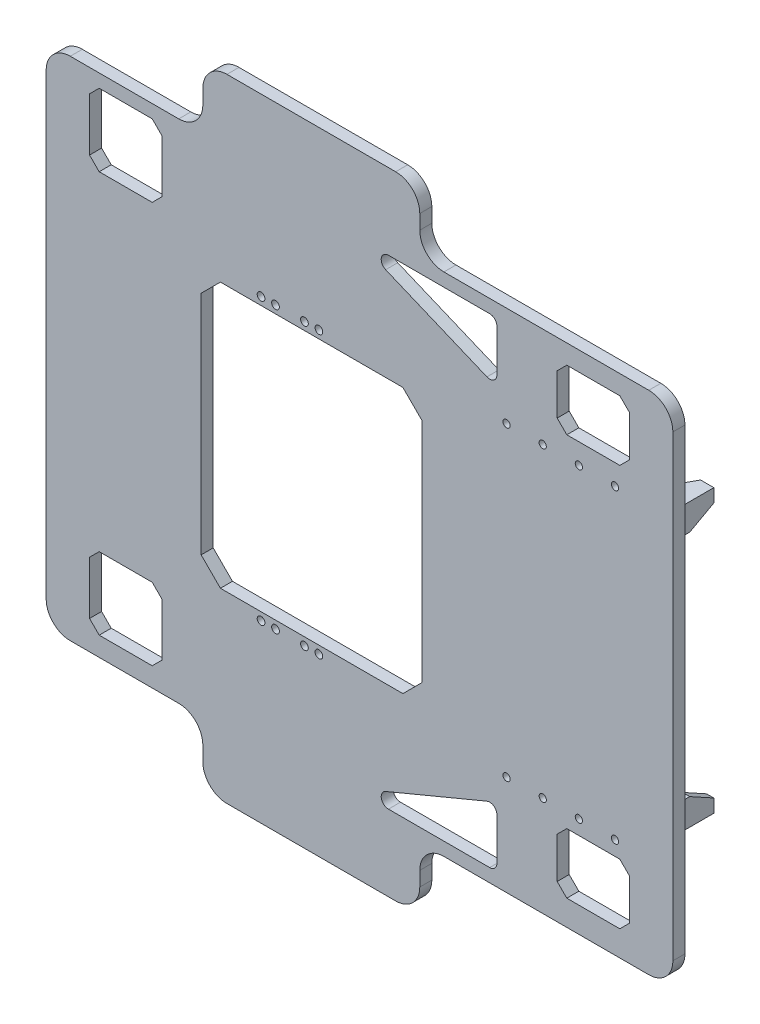
SolidWorks part; units mm, degrees
ref_plane "前视基准面" through (0, 0, 0) normal (0, 0, 1) x (1, 0, 0)
ref_plane "上视基准面" through (0, 0, 0) normal (0, 1, 0) x (1, 0, 0)
ref_plane "右视基准面" through (0, 0, 0) normal (1, 0, 0) x (0, 0, -1)
sketch "草图1" plane through (0, 0, 0) normal (0, 0, 1) x (1, 0, 0)
  line L2 (-130, 95) -> (-130, -95)
  line L3 (-120, -105) -> (-75, -105)
  line L4 (130, 95) -> (130, -95)
  line L5 (126.7518, 102.3765) -> (130, 105) construction
  line L6 (-130, -105) -> (-126.7518, -102.3765) construction
  line L9 (-65, -115) -> (-65, -121)
  line L10 (-55, -131) -> (15, -131)
  line L11 (25, -121) -> (25, -115)
  line L13 (35, -105) -> (120, -105)
  line L14 (126.7518, -102.3765) -> (130, -105) construction
  line L15 (-130, 105) -> (-126.7518, 102.3765) construction
  line L16 (-130, 0) -> (130, 0) construction
  line L17 (35, 105) -> (120, 105)
  line L18 (25, 121) -> (25, 115)
  line L19 (-55, 131) -> (15, 131)
  line L20 (-65, 115) -> (-65, 121)
  line L21 (-120, 105) -> (-75, 105)
  arc A1 (-120, -105) -> (-130, -95) centre (-120, -95) cw
  arc A3 (120, -105) -> (130, -95) centre (120, -95) ccw
  arc A8 (-65, -115) -> (-75, -105) centre (-75, -115) ccw
  arc A9 (25, -115) -> (35, -105) centre (35, -115) cw
  arc A10 (-55, -131) -> (-65, -121) centre (-55, -121) cw
  arc A11 (15, -131) -> (25, -121) centre (15, -121) ccw
  arc A12 (15, 131) -> (25, 121) centre (15, 121) cw
  arc A13 (-55, 131) -> (-65, 121) centre (-55, 121) ccw
  arc A14 (25, 115) -> (35, 105) centre (35, 115) ccw
  arc A15 (-65, 115) -> (-75, 105) centre (-75, 115) cw
  arc A16 (120, 105) -> (130, 95) centre (120, 95) cw
  arc A17 (-120, 105) -> (-130, 95) centre (-120, 95) ccw
  point P0 (0, 0)
  point P40 (25, -105)
  point P45 (25, 105)
  point P52 (29.9624, -121.8659)
  point P53 (-59.9676, -121.8041)
  dimension "D2" = 10
  dimension "D3" = 65
  dimension "D4" = 10
  dimension "D5" = 105
  dimension "D7" = 10
  dimension "D8" = 10
  dimension "D10" = 10
  dimension "D12" = 10
  dimension "D13" = 105
  dimension "D18" = 90
  dimension "D19" = 6
extrude "凸台-拉伸1" add sketch "草图1" along normal blind 5
sketch "草图2" plane through (0, 0, 5) normal (0, 0, 1) x (1, 0, 0)
  line L0 (130, -95) -> (130, 95) construction
  line L5 (10.8462, -93.7308) -> (52.8462, -76.2308)
  line L6 (-108, 99.5) -> (-86, 99.5)
  line L7 (-108, -67) -> (-86, -67)
  line L8 (-112, -71) -> (-112, -93)
  line L9 (-108, -97) -> (-86, -97)
  line L10 (-82, -71) -> (-82, -93)
  line L11 (-112, -67) -> (-82, -97) construction
  line L12 (-112, -97) -> (-82, -67) construction
  line L13 (86, 97) -> (108, 97)
  line L14 (82, 93) -> (82, 76)
  line L15 (86, 72) -> (108, 72)
  line L16 (112, 93) -> (112, 76)
  line L17 (82, 97) -> (112, 72) construction
  line L18 (82, 72) -> (112, 97) construction
  line L19 (86, -69.5) -> (108, -69.5)
  line L20 (82, -73.5) -> (82, -90.5)
  line L21 (86, -94.5) -> (108, -94.5)
  line L22 (112, -73.5) -> (112, -90.5)
  line L23 (82, -69.5) -> (112, -94.5) construction
  line L24 (82, -94.5) -> (112, -69.5) construction
  line L25 (12, 99.5) -> (54, 99.5)
  line L28 (57, 96.5) -> (57, 79)
  line L29 (10.8462, 93.7308) -> (52.8462, 76.2308)
  line L33 (12, -99.5) -> (54, -99.5)
  line L34 (57, -79) -> (57, -96.5)
  line L35 (-55, -131) -> (15, -131) construction
  line L37 (-112, 95.5) -> (-112, 73.5)
  line L38 (-120, -105) -> (-75, -105) construction
  line L39 (-130, 95) -> (-130, -95) construction
  line L40 (-108, 69.5) -> (-86, 69.5)
  line L41 (-82, 95.5) -> (-82, 73.5)
  line L42 (-112, 99.5) -> (-82, 69.5) construction
  line L43 (-112, 69.5) -> (-82, 99.5) construction
  line L44 (-112, 73.5) -> (-108, 69.5)
  line L45 (-112, 95.5) -> (-108, 99.5)
  line L46 (-86, 69.5) -> (-82, 73.5)
  line L47 (-86, 99.5) -> (-82, 95.5)
  line L48 (-108, -67) -> (-112, -71)
  line L49 (-112, -93) -> (-108, -97)
  line L50 (-86, -67) -> (-82, -71)
  line L51 (-86, -97) -> (-82, -93)
  line L52 (86, 97) -> (82, 93)
  line L53 (82, 76) -> (86, 72)
  line L54 (108, 97) -> (112, 93)
  line L55 (108, 72) -> (112, 76)
  line L56 (86, -69.5) -> (82, -73.5)
  line L57 (108, -69.5) -> (112, -73.5)
  line L58 (82, -90.5) -> (86, -94.5)
  line L59 (108, -94.5) -> (112, -90.5)
  arc A0 (57, -96.5) -> (54, -99.5) centre (54, -96.5) cw
  arc A1 (57, -79) -> (52.8462, -76.2308) centre (54, -79) ccw
  arc A2 (12, -99.5) -> (10.8462, -93.7308) centre (12, -96.5) cw
  arc A3 (10.8462, 93.7308) -> (12, 99.5) centre (12, 96.5) cw
  arc A4 (57, 96.5) -> (54, 99.5) centre (54, 96.5) ccw
  arc A5 (57, 79) -> (52.8462, 76.2308) centre (54, 79) cw
  point P0 (-97, 84.5)
  point P1 (-97, 84.5)
  point P5 (-97, -82)
  point P10 (97, 84.5)
  point P15 (97, -82)
  point P20 (27, 84.5)
  point P25 (27, -82)
  point P75 (-3, 99.5)
  point P78 (57, 99.5)
  dimension "D11" = 3
  dimension "D17" = 3
  dimension "D18" = 3
  dimension "D35" = 3
  dimension "D36" = 3
  dimension "D37" = 3
  dimension "D2" = 8
  dimension "D3" = 18
  dimension "D4" = 30
  dimension "D5" = 25
  dimension "D6" = 30
  dimension "D7" = 18
  dimension "D8" = 18
  dimension "D9" = 25
  dimension "D10" = 30
  dimension "D12" = 60
  dimension "D13" = 25
  dimension "D14" = 30
  dimension "D15" = 25
  dimension "D19" = 42
  dimension "D20" = 17.5
  dimension "D38" = 17.5
  dimension "D39" = 31.5
extrude "切除-拉伸1" cut sketch "草图2" against normal through all
sketch "草图3" plane through (0, 0, 0) normal (0, 0, -1) x (-1, 0, 0)
  line L0 (130, 95) -> (130, -95) construction
  line L1 (57.7, 55) -> (-18, 55)
  line L2 (65.7, 47) -> (65.7, -47)
  line L3 (57.7, -55) -> (-18, -55)
  line L4 (-26, 47) -> (-26, -47)
  line L5 (65.7, 55) -> (-26, -55) construction
  line L6 (65.7, -55) -> (-26, 55) construction
  line L7 (-26, -47) -> (-18, -55)
  line L8 (-18, 55) -> (-26, 47)
  line L9 (65.7, -47) -> (57.7, -55)
  line L10 (57.7, 55) -> (65.7, 47)
  point P0 (19.85, 0)
  dimension "D1" = 64.3
  dimension "D2" = 91.7
  dimension "D3" = 110
extrude "切除-拉伸2" cut sketch "草图3" against normal through all
sketch "草图4" plane through (0, 0, 0) normal (0, 0, -1) x (-1, 0, 0)
  line L0 (-46, -47.5) -> (-46, -58.5)
  line L1 (-46, -58.5) -> (-57, -58.5)
  line L2 (-57, -58.5) -> (-57, -55.5)
  line L3 (-57, -55.5) -> (-49, -55.5)
  line L4 (-49, -55.5) -> (-49, -47.5)
  line L5 (-49, -47.5) -> (-46, -47.5)
  line L6 (-26, 47) -> (-26, -47) construction
  line L8 (-26, 0) -> (-130, 0) construction
  line L9 (-26, 47) -> (-26, -47) construction
  line L10 (-130, -95) -> (-130, 95) construction
  dimension "D1" = 11
  dimension "D2" = 11
  dimension "D3" = 3
  dimension "D4" = 3
  dimension "D5" = 20
  dimension "D6" = 55.5
extrude "凸台-拉伸2" add sketch "草图4" along normal blind 20
sketch "草图5" plane through (0, -58.5, 0) normal (0, -1, 0) x (1, 0, 0)
  line L0 (57, -10) -> (51.5, -20)
  line L1 (57, -20) -> (57, 0) construction
  line L2 (57, -20) -> (46, -20) construction
  line L3 (51.5, -20) -> (57, -20)
  line L4 (57, -20) -> (57, -10)
  dimension "D1" = 10
  dimension "D2" = 5.5
extrude "切除-拉伸3" cut sketch "草图5" against normal blind 10
sketch "草图6" plane through (46, 0, 0) normal (-1, 0, 0) x (0, 0, 1)
  line L0 (-20, -53) -> (-10, -47.5)
  line L1 (-20, -58.5) -> (-20, -47.5) construction
  line L2 (-20, -47.5) -> (0, -47.5) construction
  line L3 (-10, -47.5) -> (-20, -47.5)
  line L4 (-20, -47.5) -> (-20, -53)
  dimension "D1" = 10
  dimension "D2" = 5.5
extrude "切除-拉伸4" cut sketch "草图6" against normal blind 10
ref_plane "基准面2" through (84, 0, 0) normal (1, 0, 0) x (0, 0, -1)
mirror "镜向1" about plane through (84, 0, 0) normal (1, 0, 0) of "凸台-拉伸2", "切除-拉伸4", "切除-拉伸3"
mirror "镜向2" about plane through (0, 0, 0) normal (0, 1, 0) of "镜向1"
sketch "草图7" plane through (0, 0, 0) normal (0, 0, -1) x (-1, 0, 0)
  line L0 (65.7, -47) -> (65.7, 47) construction
  line L1 (-18, -55) -> (57.7, -55) construction
  circle A0 centre (16.85, -58.25) radius 1.6
  circle A1 centre (22.85, -58.25) radius 1.6
  circle A2 centre (40.85, -58.25) radius 1.6
  circle A3 centre (34.85, -58.25) radius 1.6
  dimension "D1" = 3.2
  dimension "D2" = 3.2
  dimension "D3" = 3.2
  dimension "D4" = 3.2
  dimension "D6" = 6
  dimension "D7" = 6
  dimension "D8" = 30.85
  dimension "D9" = 3.25
  dimension "D5" = 18
extrude "切除-拉伸5" cut sketch "草图7" against normal through all
mirror "镜向3" about plane through (0, 0, 0) normal (0, 1, 0) of "切除-拉伸5"
sketch "草图8" plane through (0, 0, 0) normal (0, 0, -1) x (-1, 0, 0)
  line L0 (-46, -58.5) -> (-46, -53) construction
  line L2 (-57, -55.5) -> (-51.5, -55.5) construction
  line L3 (-130, 0) -> (-26, 0) construction
  line L4 (-130, -95) -> (-130, 95) construction
  line L5 (-26, 47) -> (-26, -47) construction
  circle A0 centre (-61, -63.5) radius 1.5
  circle A4 centre (-76, -63.5) radius 1.5
  circle A5 centre (-91, -63.5) radius 1.5
  circle A6 centre (-106, -63.5) radius 1.5
  circle A7 centre (-106, 63.5) radius 1.5
  circle A8 centre (-91, 63.5) radius 1.5
  circle A9 centre (-76, 63.5) radius 1.5
  circle A10 centre (-61, 63.5) radius 1.5
  dimension "D1" = 4
  dimension "D2" = 3
  dimension "D3" = 15
  dimension "D4" = 8
extrude "切除-拉伸6" cut sketch "草图8" against normal through all
equation "\"45、\"=43.7672"
